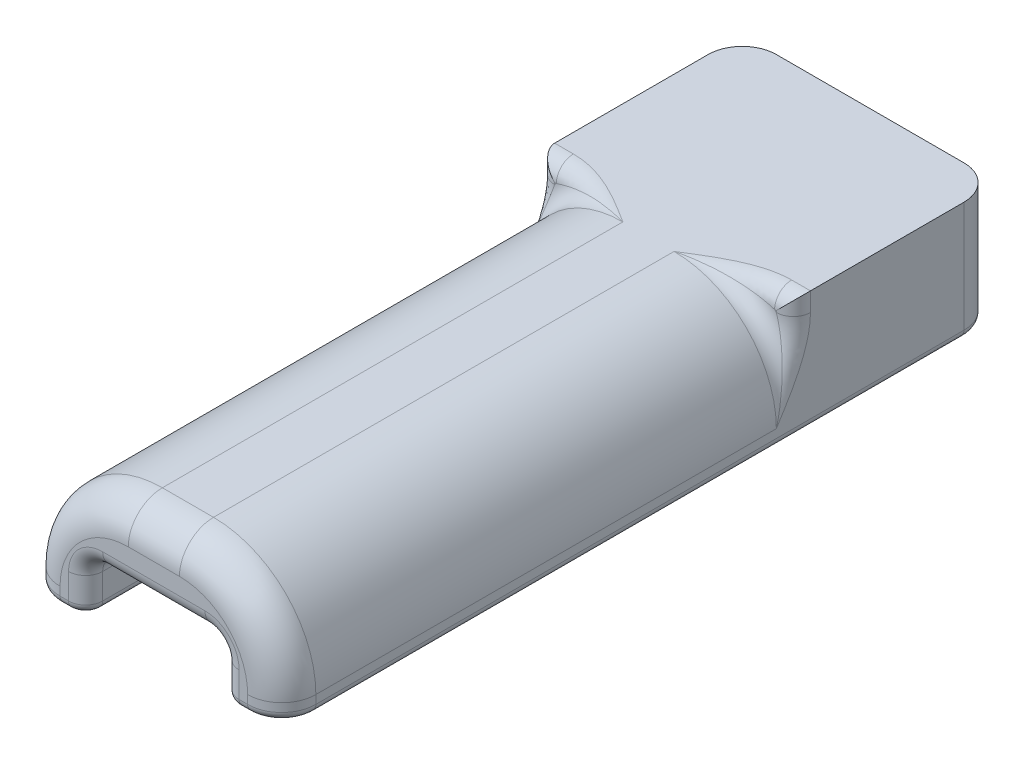
SolidWorks part; units mm, degrees
ref_plane "Front Plane" through (0, 0, 0) normal (0, 0, 1) x (1, 0, 0)
ref_plane "Top Plane" through (0, 0, 0) normal (0, 1, 0) x (1, 0, 0)
ref_plane "Right Plane" through (0, 0, 0) normal (1, 0, 0) x (0, 0, -1)
sketch "Sketch1" plane through (0, 0, 0) normal (0, 1, 0) x (1, 0, 0)
  line L1 (-7.5, 21) -> (7.5, 21)
  line L2 (-7.5, 21) -> (-7.5, -21)
  line L3 (-7.5, -21) -> (7.5, -21)
  line L4 (7.5, 21) -> (7.5, -21)
  line L5 (-7.5, 21) -> (7.5, -21) construction
  line L6 (-7.5, -21) -> (7.5, 21) construction
  point P0 (0, 0)
  dimension "D1" = 15
  dimension "D2" = 42
extrude "Boss-Extrude1" add sketch "Sketch1" along normal blind 7
fillet "Fillet1" radius 6 2 edges at (7.5, 7, 0) (-7.5, 7, 0)
sketch "Sketch2" plane through (0, 0, -21) normal (0, 0, -1) x (-1, 0, 0)
  line L1 (-7.5, 0) -> (7.5, 0)
  line L2 (-7.5, 0) -> (-7.5, 7)
  line L3 (-7.5, 7) -> (7.5, 7)
  line L4 (7.5, 0) -> (7.5, 7)
  line L5 (-1.5, 7) -> (1.5, 7) construction
extrude "Boss-Extrude2" add sketch "Sketch2" against normal blind 12
fillet "Fillet2" radius 1 6 edges at (-4.5, 7, -9) (-5.7426, 5.2426, -9) (-7.5, 4, -9) (7.5, 4, -9) (5.7426, 5.2426, -9) (4.5, 7, -9)
fillet "Fillet3" radius 2 2 edges at (-7.5, 3.5, -21) (7.5, 3.5, -21)
fillet "Fillet4" radius 2 5 edges at (-7.5, 0.5, 21) (-5.7426, 5.2426, 21) (7.5, 0.5, 21) (5.7426, 5.2426, 21) (0, 7, 21)
sketch "Sketch3" plane through (0, 0, 0) normal (0, -1, 0) x (1, 0, 0)
  line L0 (-5.5, 21) -> (5.5, 21) construction
  line L1 (-4, 21) -> (4, 21)
  line L2 (-4, 21) -> (-4, -4)
  line L3 (-4, -4) -> (4, -4)
  line L4 (4, 21) -> (4, -4)
  point P6 (0, 21)
  point P7 (0, 21)
  dimension "D1" = 8
  dimension "D2" = 25
extrude "Cut-Extrude1" cut sketch "Sketch3" against normal blind 3
fillet "Fillet5" radius 1 8 edges at (4, 1.5, 21) (-4, 1.5, 21) (0, 3, 21) (4, 3, 8.5) (0, 3, -4) (-4, 3, 8.5) (4, 1.5, -4) (-4, 1.5, -4)
fillet "Fillet6" radius 0.5 16 edges at (6.9142, 0, 20.4142) (7.5, 0, 0) (6.9142, 0, -20.4142) (0, 0, -21) (-6.9142, 0, -20.4142) (-7.5, 0, 0) (-6.9142, 0, 20.4142) (-5.25, 0, 21) (-4.2929, 0, 20.7071) (-4, 0, 8.5) (-3.7071, 0, -3.7071) (0, 0, -4) (3.7071, 0, -3.7071) (4, 0, 8.5) (4.2929, 0, 20.7071) (5.25, 0, 21)
